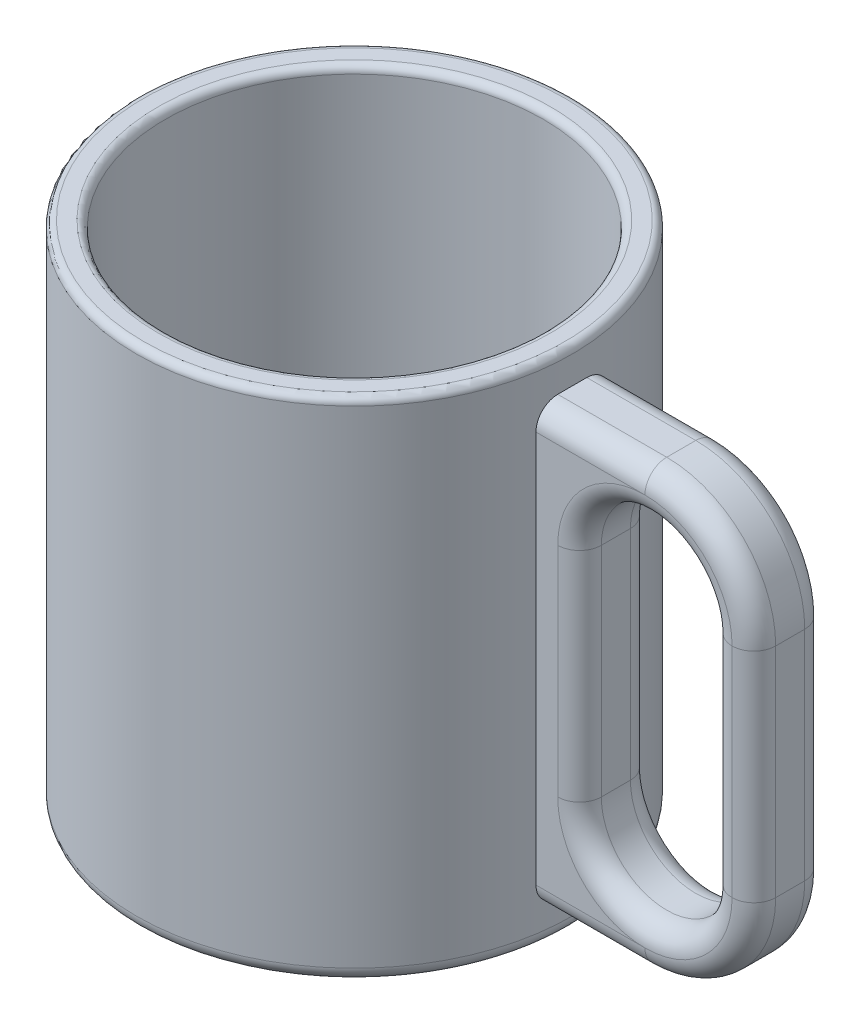
SolidWorks part; units mm, degrees
ref_plane "정면" through (0, 0, 0) normal (0, 0, 1) x (1, 0, 0)
ref_plane "윗면" through (0, 0, 0) normal (0, 1, 0) x (1, 0, 0)
ref_plane "우측면" through (0, 0, 0) normal (1, 0, 0) x (0, 0, -1)
sketch "스케치1" plane through (0, 0, 0) normal (0, 1, 0) x (1, 0, 0)
  circle A0 centre (-21.5891, 0) radius 30
  circle A1 centre (-21.5891, 0) radius 26
extrude "보스-돌출1" add sketch "스케치1" along normal blind 70
sketch "스케치2" plane through (0, 0, 0) normal (0, -1, 0) x (1, 0, 0)
  circle A0 centre (-21.5891, 0) radius 26
extrude "보스-돌출2" add sketch "스케치2" against normal blind 2
fillet "필렛2" radius 1 3 edges at (-21.5891, 2, -26) (-21.5891, 70, 26) (-21.5891, 70, 30)
fillet "필렛3" radius 2 1 edges at (-21.5891, 0, 30)
sketch "스케치3" plane through (0, 0, 0) normal (0, 0, 1) x (1, 0, 0)
  line L0 (8.4109, 2) -> (8.4109, 69) construction
  line L2 (8.4109, 65.2069) -> (23.4109, 65.2069)
  line L3 (8.4109, 65.2069) -> (8.4109, 5.2069)
  line L4 (8.4109, 5.2069) -> (23.4109, 5.2069)
  line L5 (38.4109, 50.2069) -> (38.4109, 20.2069)
  line L17 (14.4109, 50.2069) -> (32.4109, 50.2069)
  line L18 (14.4109, 50.2069) -> (14.4109, 20.2069)
  line L19 (14.4109, 20.2069) -> (32.4109, 20.2069)
  line L20 (32.4109, 50.2069) -> (32.4109, 20.2069)
  arc A2 (23.4109, 5.2069) -> (38.4109, 20.2069) centre (23.4109, 20.2069) ccw
  arc A3 (38.4109, 50.2069) -> (23.4109, 65.2069) centre (23.4109, 50.2069) ccw
  arc A4 (32.4109, 20.2069) -> (14.4109, 20.2069) centre (23.4109, 20.2069) cw
  arc A5 (32.4109, 50.2069) -> (14.4109, 50.2069) centre (23.4109, 50.2069) ccw
  point P22 (38.4109, 5.2069)
  dimension "D3" = 15
  dimension "D1" = 30
  dimension "D2" = 60
  dimension "D4" = 18
  dimension "D5" = 30
  dimension "D6" = 6
  dimension "D7" = 15
extrude "보스-돌출5" add sketch "스케치3" along normal blind 5 and the other way blind 5 contours L5 A3 L2 L3 L4 A2 A5 L20 A4 L18 region at (15.9109, 64.5361, 0)
fillet "필렛6" radius 3 8 edges at (23.4109, 59.2069, -5) (32.4109, 35.2069, -5) (23.4109, 11.2069, -5) (32.4109, 35.2069, 5) (14.4109, 35.2069, -5) (23.4109, 11.2069, 5) (14.4109, 35.2069, 5) (23.4109, 59.2069, 5)
fillet "필렛7" radius 3 10 edges at (15.9109, 5.2069, -5) (34.0175, 9.6003, -5) (38.4109, 35.2069, -5) (15.9109, 65.2069, -5) (15.9109, 5.2069, 5) (34.0175, 9.6003, 5) (38.4109, 35.2069, 5) (15.9109, 65.2069, 5) (34.0175, 60.8135, -5) (34.0175, 60.8135, 5)
